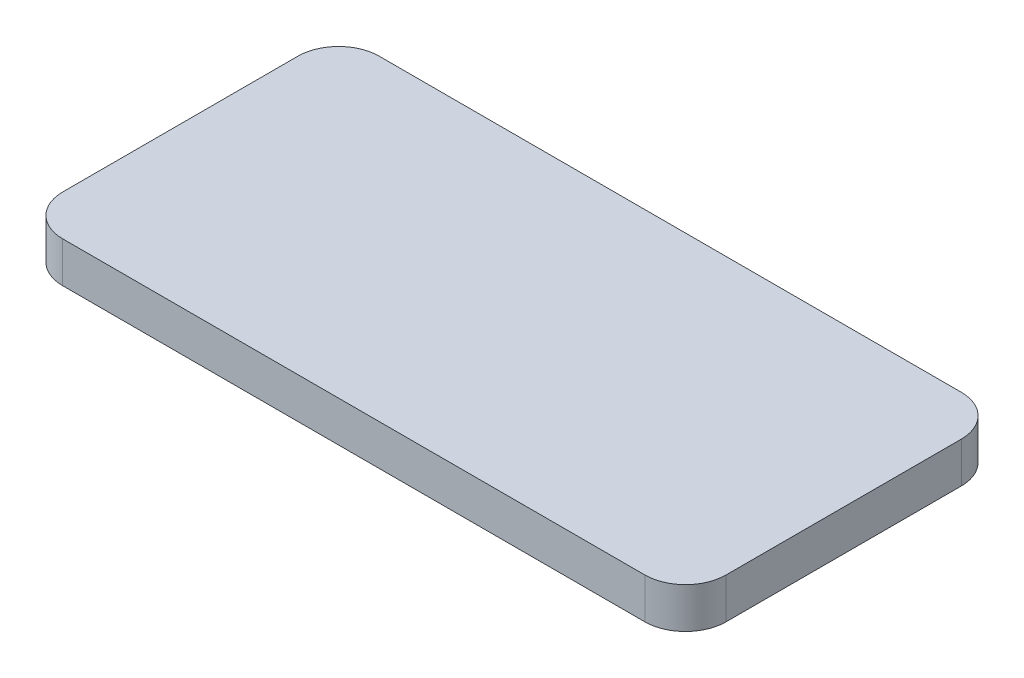
SolidWorks part; units mm, degrees
ref_plane "前视基准面" through (0, 0, 0) normal (0, 0, 1) x (1, 0, 0)
ref_plane "上视基准面" through (0, 0, 0) normal (0, 1, 0) x (1, 0, 0)
ref_plane "右视基准面" through (0, 0, 0) normal (1, 0, 0) x (0, 0, -1)
other "Configuration Table"
sketch "草图1" plane through (0, 0, 0) normal (0, 1, 0) x (1, 0, 0)
  line L1 (10, 0) -> (153.3, 0)
  line L2 (0, 10) -> (0, 67.9)
  line L3 (10, 77.9) -> (153.3, 77.9)
  line L4 (163.3, 10) -> (163.3, 67.9)
  arc A0 (153.3, 0) -> (163.3, 10) centre (153.3, 10) ccw
  arc A1 (153.3, 77.9) -> (163.3, 67.9) centre (153.3, 67.9) cw
  arc A2 (10, 0) -> (0, 10) centre (10, 10) cw
  arc A3 (0, 67.9) -> (10, 77.9) centre (10, 67.9) cw
  point P9 (163.3, 77.9)
  point P12 (0, 0)
  point P15 (0, 77.9)
  dimension "D3" = 10
  dimension "D1" = 77.9
  dimension "D2" = 163.3
extrude "凸台-拉伸1" add sketch "草图1" along normal blind 10 contours L3 A1 L4 A0 L1 A2 L2 A3
sketch "草图2" plane through (0, 0, 0) normal (0, 1, 0) x (1, 0, 0)
  line L1 (0, 38.95) -> (10.073, 38.95) construction
  line L2 (0, 10) -> (0, 67.9) construction
  circle A1 centre (10.073, 38.95) radius 2
  dimension "D1" = 4
sketch "草图3" plane through (163.3, 0, 0) normal (1, 0, 0) x (0, 0, -1)
  line L2 (38.95, 10) -> (38.95, 6.6735) construction
  line L3 (10, 10) -> (67.9, 10) construction
  line L4 (10, 0) -> (67.9, 0) construction
  line L6 (35.4215, 3.3265) -> (42.4785, 3.3265)
  line L7 (35.4215, 3.3265) -> (35.4215, 6.6735)
  line L8 (35.4215, 6.6735) -> (42.4785, 6.6735)
  line L9 (42.4785, 3.3265) -> (42.4785, 6.6735)
  line L14 (38.95, 3.3265) -> (38.95, 0) construction
  line L15 (42.4785, 5) -> (70.4892, 5) construction
  circle A0 centre (49.0469, 5) radius 0.988
  arc A1 (35.4215, 6.6735) -> (35.4215, 3.3265) centre (35.4215, 5) ccw
  arc A2 (42.4785, 3.3265) -> (42.4785, 6.6735) centre (42.4785, 5) ccw
  ellipse E0 centre (15.582, 5) end of major axis (11.582, 5) minor radius 3
  point P52 (38.95, 5)
  point P59 (11.582, 5)
  dimension "D2" = 3
  dimension "D3" = 8
sketch "草图5" plane through (163.3, 0, 0) normal (1, 0, 0) x (0, 0, -1)
sketch "草图6" plane through (0, 0, 0) normal (1, 0, 0) x (0, 0, -1)
  line L0 (10, 5) -> (33.748, 5) construction
  line L1 (10, 10) -> (10, 0) construction
  arc A0 (35.4215, 6.6735) -> (35.4215, 3.3265) centre (35.4215, 5) ccw construction
